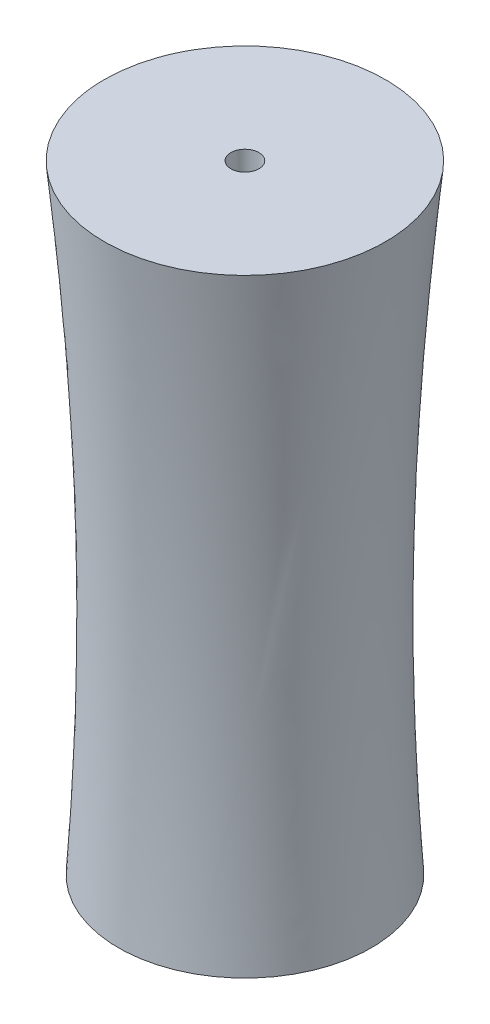
SolidWorks part; units mm, degrees
ref_plane "Front Plane" through (0, 0, 0) normal (0, 0, 1) x (1, 0, 0)
ref_plane "Top Plane" through (0, 0, 0) normal (0, 1, 0) x (1, 0, 0)
ref_plane "Right Plane" through (0, 0, 0) normal (1, 0, 0) x (0, 0, -1)
sketch "Sketch2" plane through (0, 0, 0) normal (0, 1, 0) x (1, 0, 0)
  circle A0 centre (0, 0) radius 5
  dimension "D1" = 10
ref_plane "Plane1" through (0, -22, 0) normal (0, 1, 0) x (1, 0, 0)
sketch "Sketch3" plane through (0, -22, 0) normal (0, 1, 0) x (1, 0, 0)
  circle A0 centre (0, 0) radius 4.5
  dimension "D1" = 9
loft "Loft1" add profiles "Sketch2", "Sketch3" connector at (4.9348, 0, 0.8049) connector at (2.156, -22, 3.9499)
sketch "Sketch4" plane through (0, 0, 0) normal (0, 1, 0) x (1, 0, 0)
  circle A0 centre (0, 0) radius 0.5
  dimension "D1" = 1
extrude "Cut-Extrude1" cut sketch "Sketch4" against normal through all
sketch "Sketch5" plane through (0, -22, 0) normal (0, -1, 0) x (1, 0, 0)
  circle A0 centre (0, 0) radius 2.5
  dimension "D1" = 5
extrude "Cut-Extrude2" cut sketch "Sketch5" against normal blind 2
